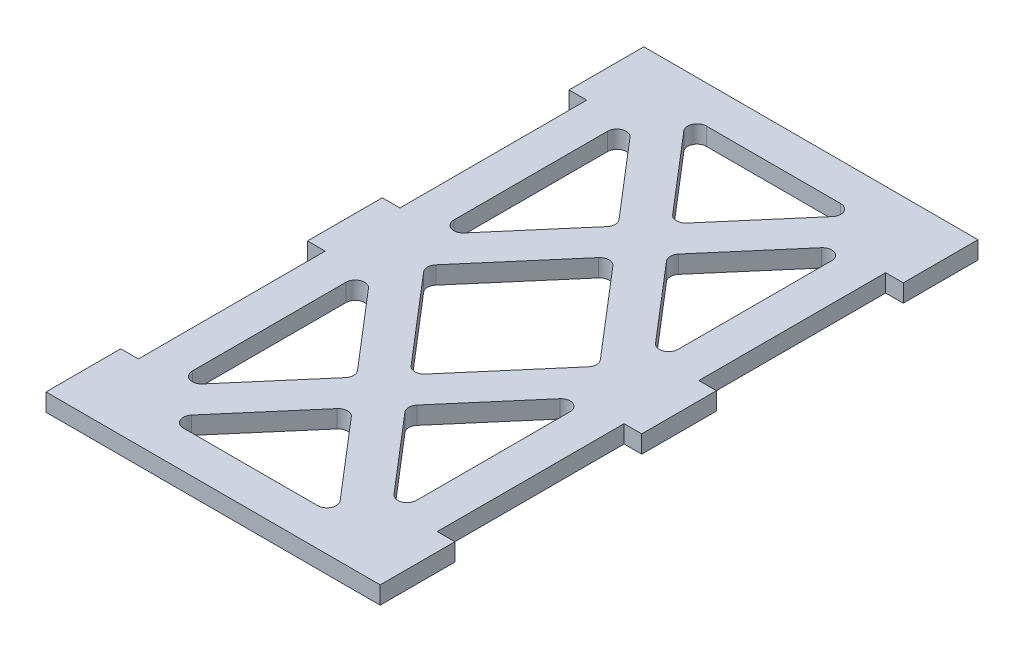
SolidWorks part; units mm, degrees
material "Custom Plastic"
ref_plane "Front Plane" through (0, 0, 0) normal (0, 0, 1) x (1, 0, 0)
ref_plane "Top Plane" through (0, 0, 0) normal (0, 1, 0) x (1, 0, 0)
ref_plane "Right Plane" through (0, 0, 0) normal (1, 0, 0) x (0, 0, -1)
sketch "Sketch1" plane through (0, 0, 0) normal (0, 1, 0) x (1, 0, 0)
  line L1 (-25.4, -50.8) -> (25.4, -50.8)
  line L2 (-25.4, -50.8) -> (-25.4, 50.8)
  line L3 (-25.4, 50.8) -> (25.4, 50.8)
  line L4 (25.4, -50.8) -> (25.4, 50.8)
  line L5 (-25.4, -50.8) -> (25.4, 50.8) construction
  line L6 (-25.4, 50.8) -> (25.4, -50.8) construction
  point P0 (0, 0)
  dimension "D1" = 50.8
  dimension "D2" = 101.6
extrude "Boss-Extrude1" add sketch "Sketch1" along normal blind 2.9972
sketch "Sketch2" plane through (0, 2.9972, 0) normal (0, 1, 0) x (1, 0, 0)
  line L0 (25.4, 6.35) -> (28.3972, 6.35)
  line L1 (25.4, 50.8) -> (28.3972, 50.8)
  line L2 (25.4, 50.8) -> (25.4, 38.1)
  line L3 (25.4, 38.1) -> (28.3972, 38.1)
  line L4 (28.3972, 50.8) -> (28.3972, 38.1)
  line L5 (25.4, 6.35) -> (25.4, -6.35)
  line L6 (25.4, -6.35) -> (28.3972, -6.35)
  line L7 (28.3972, 6.35) -> (28.3972, -6.35)
  line L8 (25.4, -38.1) -> (28.3972, -38.1)
  line L9 (25.4, -38.1) -> (25.4, -50.8)
  line L10 (25.4, -50.8) -> (28.3972, -50.8)
  line L11 (28.3972, -38.1) -> (28.3972, -50.8)
  line L12 (-28.3972, 6.35) -> (-25.4, 6.35)
  line L13 (-28.3972, 6.35) -> (-28.3972, -6.35)
  line L14 (-28.3972, -6.35) -> (-25.4, -6.35)
  line L15 (-25.4, 6.35) -> (-25.4, -6.35)
  line L16 (-28.3972, -38.1) -> (-25.4, -38.1)
  line L17 (-28.3972, -38.1) -> (-28.3972, -50.8)
  line L18 (-28.3972, -50.8) -> (-25.4, -50.8)
  line L19 (-25.4, -38.1) -> (-25.4, -50.8)
  line L20 (-28.3972, 50.8) -> (-25.4, 50.8)
  line L21 (-28.3972, 50.8) -> (-28.3972, 38.1)
  line L22 (-28.3972, 38.1) -> (-25.4, 38.1)
  line L23 (-25.4, 50.8) -> (-25.4, 38.1)
  line L24 (25.4, -50.8) -> (25.4, 50.8) construction
  line L25 (-25.4, -50.8) -> (25.4, -50.8) construction
  dimension "D1" = 2.9972
  dimension "D2" = 12.7
  dimension "D3" = 3
  dimension "D4" = 2
extrude "Boss-Extrude2" add sketch "Sketch2" against normal blind 2.9972
sketch "Sketch3" plane through (0, 2.9972, 0) normal (0, 1, 0) x (1, 0, 0)
  line L0 (-25.4, 38.1) -> (-25.4, 6.35) construction
  line L1 (-19.05, 44.45) -> (19.05, 44.45)
  line L2 (-19.05, 44.45) -> (-19.05, -44.45)
  line L3 (-19.05, -44.45) -> (19.05, -44.45)
  line L4 (19.05, 44.45) -> (19.05, -44.45)
  line L5 (25.4, 6.35) -> (25.4, 38.1) construction
  line L6 (28.3972, 50.8) -> (-28.3972, 50.8) construction
  line L7 (-28.3972, -50.8) -> (28.3972, -50.8) construction
  dimension "D1" = 6.35
  dimension "D2" = 6.35
  dimension "D3" = 6.35
  dimension "D4" = 6.35
extrude "Cut-Extrude1" cut sketch "Sketch3" against normal through all
sketch "Sketch4" plane through (0, 2.9972, 0) normal (0, 1, 0) x (1, 0, 0)
  line L0 (-19.05, -44.45) -> (19.05, 0)
  line L1 (19.05, -44.45) -> (19.05, 44.45) construction
  line L2 (19.05, 0) -> (-19.05, 44.45)
  line L3 (19.05, 44.45) -> (-19.05, 0)
  line L4 (-19.05, 44.45) -> (-19.05, -44.45) construction
  line L5 (-19.05, 0) -> (19.05, -44.45)
extrude "Extrude-Thin1" add sketch "Sketch4" against normal up to surface (2.9972 mm away) thin up to face at (0, 0, 0) thin type mid plane wall 6.35
fillet "Fillet1" radius 1.5875 22 edges at (14.8683, 1.4986, 0) (0, 1.4986, -17.3463) (0, 1.4986, 17.3463) (-4.1817, 1.4986, 22.225) (-19.05, 1.4986, 4.8787) (-19.05, 1.4986, 39.5713) (19.05, 1.4986, -39.5713) (4.1817, 1.4986, -22.225) (19.05, 1.4986, -4.8787) (-19.05, 1.4986, -4.8787) (-4.1817, 1.4986, -22.225) (-19.05, 1.4986, -39.5713) (14.8683, 1.4986, 44.45) (0, 1.4986, 27.1037) (-14.8683, 1.4986, 44.45) (0, 1.4986, -27.1037) (14.8683, 1.4986, -44.45) (-14.8683, 1.4986, -44.45) (4.1817, 1.4986, 22.225) (19.05, 1.4986, 39.5713) (19.05, 1.4986, 4.8787) (-14.8683, 1.4986, 0)
